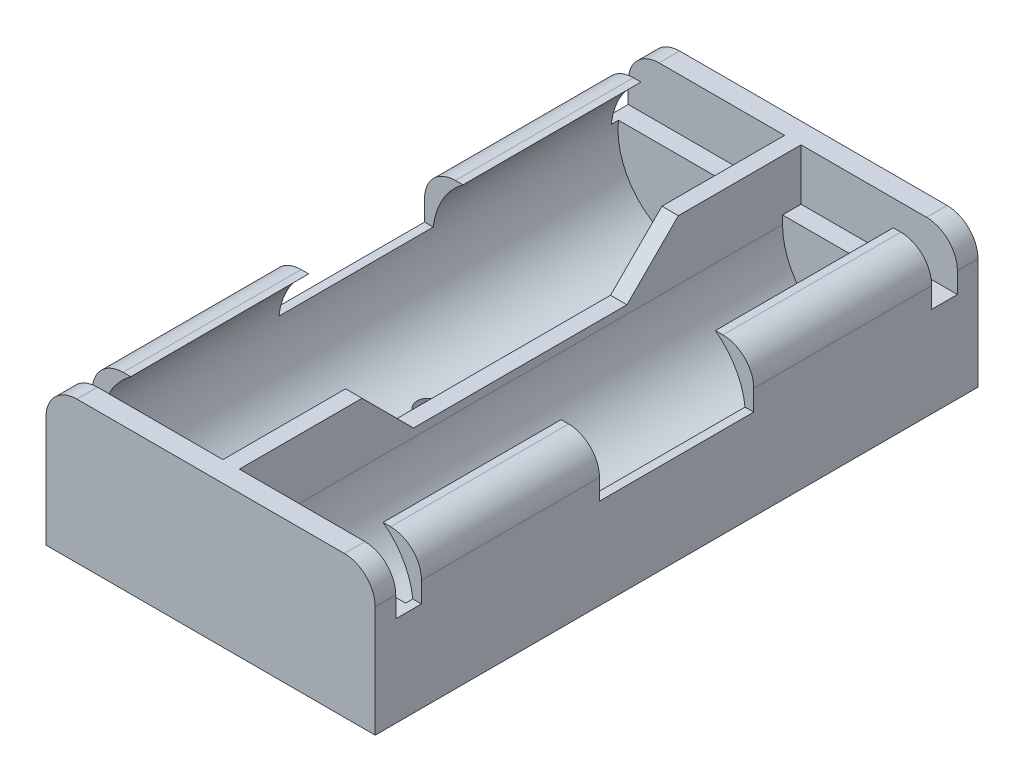
SolidWorks part; units mm, degrees
ref_plane "Front Plane" through (0, 0, 0) normal (0, 0, 1) x (1, 0, 0)
ref_plane "Top Plane" through (0, 0, 0) normal (0, 1, 0) x (1, 0, 0)
ref_plane "Right Plane" through (0, 0, 0) normal (1, 0, 0) x (0, 0, -1)
sketch "Sketch1" plane through (0, 0, 0) normal (0, 0, 1) x (1, 0, 0)
  line L1 (0, 0) -> (40.64, 0)
  line L2 (0, 0) -> (0, 17.526)
  line L3 (0, 17.526) -> (40.64, 17.526)
  line L4 (40.64, 0) -> (40.64, 17.526)
  line L5 (0, 0) -> (40.64, 17.526) construction
  line L6 (0, 17.526) -> (40.64, 0) construction
  point P4 (20.32, 8.763)
  dimension "D1" = 17.526
  dimension "D2" = 40.64
extrude "Boss-Extrude1" add sketch "Sketch1" along normal mid plane 74.422
sketch "Sketch2" plane through (0, 0, 0) normal (0, 0, 1) x (1, 0, 0)
  line L0 (0, 0) -> (40.64, 0) construction
  line L1 (19.304, 10.16) -> (21.336, 10.16) construction
  line L2 (19.304, 10.16) -> (19.304, 17.526)
  line L3 (40.64, 17.526) -> (0, 17.526) construction
  line L4 (19.304, 17.526) -> (15.578, 17.526)
  line L5 (21.336, 10.16) -> (21.336, 17.526)
  line L6 (21.336, 17.526) -> (25.062, 17.526)
  arc A0 (15.578, 17.526) -> (19.304, 10.16) centre (10.16, 10.16) ccw
  arc A1 (21.336, 10.16) -> (25.062, 17.526) centre (30.48, 10.16) ccw
  point P5 (20.32, 0)
  point P10 (20.32, 10.16)
  dimension "D1" = 18.288
  dimension "D2" = 20.32
  dimension "D3" = 10.16
extrude "Cut-Extrude1" cut sketch "Sketch2" against normal mid plane 64.77
fillet "Fillet1" radius 3.81 2 edges at (0, 17.526, 0) (40.64, 17.526, 0)
sketch "Sketch3" plane through (40.64, 0, 0) normal (1, 0, 0) x (0, 0, -1)
  line L0 (-37.211, 17.526) -> (37.211, 17.526) construction
  line L1 (-34.671, 17.526) -> (-31.496, 17.526)
  line L2 (-34.671, 17.526) -> (-34.671, 11.176)
  line L3 (-34.671, 11.176) -> (-31.496, 11.176)
  line L4 (-31.496, 17.526) -> (-31.496, 11.176)
  line L5 (-34.671, 17.526) -> (-31.496, 11.176) construction
  line L6 (-34.671, 11.176) -> (-31.496, 17.526) construction
  line L7 (-37.211, 0) -> (-37.211, 13.716) construction
  line L8 (-9.525, 17.526) -> (9.525, 17.526)
  line L9 (-9.525, 17.526) -> (-9.525, 11.176)
  line L10 (-9.525, 11.176) -> (9.525, 11.176)
  line L11 (9.525, 17.526) -> (9.525, 11.176)
  line L12 (-9.525, 17.526) -> (9.525, 11.176) construction
  line L13 (-9.525, 11.176) -> (9.525, 17.526) construction
  line L14 (31.496, 17.526) -> (34.671, 17.526)
  line L15 (31.496, 17.526) -> (31.496, 11.176)
  line L16 (31.496, 11.176) -> (34.671, 11.176)
  line L17 (34.671, 17.526) -> (34.671, 11.176)
  line L18 (31.496, 17.526) -> (34.671, 11.176) construction
  line L19 (31.496, 11.176) -> (34.671, 17.526) construction
  line L21 (37.211, 0) -> (37.211, 13.716) construction
  point P4 (-33.0835, 14.351)
  point P11 (0, 14.351)
  point P16 (33.0835, 14.351)
  dimension "D1" = 6.35
  dimension "D2" = 3.175
  dimension "D3" = 19.05
  dimension "D4" = 2.54
  dimension "D5" = 2.54
extrude "Cut-Extrude2" cut sketch "Sketch3" against normal through all
chamfer "Chamfer1" distance 10 angle 45 2 edges at (20.32, 17.526, -9.525) (20.32, 17.526, 9.525)
sketch "Sketch4" plane through (0, 0, 0) normal (0, 1, 0) x (1, 0, 0)
  line L0 (1.0726, 9.525) -> (1.0726, -9.525) construction
  line L3 (39.5674, -9.525) -> (39.5674, 9.525) construction
  circle A0 centre (10.2166, 0) radius 1.5875
  circle A1 centre (30.4234, 0) radius 1.5875
  dimension "D1" = 3.175
  dimension "D2" = 9.144
  dimension "D3" = 9.144
sketch "Sketch5" plane through (0, 0, 0) normal (0, -1, 0) x (1, 0, 0)
  line L4 (0, -37.211) -> (40.64, -37.211)
  line L5 (40.64, -37.211) -> (40.64, 37.211)
  line L6 (40.64, 37.211) -> (0, 37.211)
  line L7 (0, 37.211) -> (0, -37.211)
  line L8 (0, -37.211) -> (40.64, -37.211)
  line L9 (40.64, -37.211) -> (40.64, 37.211)
  line L10 (40.64, 37.211) -> (0, 37.211)
  line L11 (0, 37.211) -> (0, -37.211)
  circle A0 centre (30.4234, 0) radius 1.5875 construction
  circle A1 centre (30.4234, 0) radius 1.5875
  circle A2 centre (10.2166, 0) radius 1.5875 construction
  circle A3 centre (10.2166, 0) radius 1.5875
  dimension "D1" = 0
extrude "Cut-Extrude7" cut sketch "Sketch5" against normal through all both and the other way through all contours A3 | A1
sketch "Sketch6" plane through (0, 0, -31.496) normal (0, 0, -1) x (-1, 0, 0)
  line L4 (-21.336, 11.176) -> (-19.304, 11.176)
  line L5 (-19.304, 11.176) -> (-19.304, 17.526)
  line L6 (-19.304, 17.526) -> (-21.336, 17.526)
  line L7 (-21.336, 17.526) -> (-21.336, 11.176)
  line L8 (-21.336, 11.176) -> (-19.304, 11.176)
  line L9 (-19.304, 11.176) -> (-19.304, 17.526)
  line L10 (-19.304, 17.526) -> (-21.336, 17.526)
  line L11 (-21.336, 17.526) -> (-21.336, 11.176)
  dimension "D1" = 0
extrude "Boss-Extrude2" add sketch "Sketch6" along normal up to next
sketch "Sketch7" plane through (0, 0, 31.496) normal (0, 0, 1) x (1, 0, 0)
  line L4 (21.336, 17.526) -> (19.304, 17.526)
  line L5 (19.304, 17.526) -> (19.304, 11.176)
  line L6 (19.304, 11.176) -> (21.336, 11.176)
  line L7 (21.336, 11.176) -> (21.336, 17.526)
  line L8 (21.336, 17.526) -> (19.304, 17.526)
  line L9 (19.304, 17.526) -> (19.304, 11.176)
  line L10 (19.304, 11.176) -> (21.336, 11.176)
  line L11 (21.336, 11.176) -> (21.336, 17.526)
  dimension "D1" = 0
extrude "Boss-Extrude3" add sketch "Sketch7" along normal up to next
